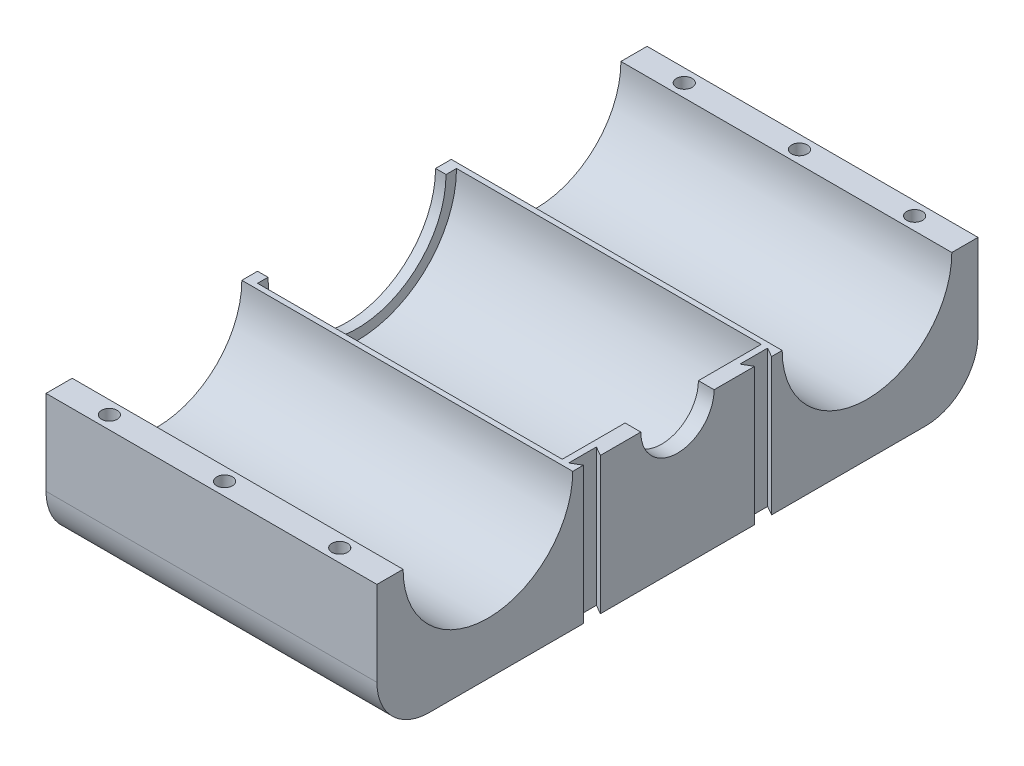
SolidWorks part; units mm, degrees
ref_plane "Front Plane" through (0, 0, 0) normal (0, 0, 1) x (1, 0, 0)
ref_plane "Top Plane" through (0, 0, 0) normal (0, 1, 0) x (1, 0, 0)
ref_plane "Right Plane" through (0, 0, 0) normal (1, 0, 0) x (0, 0, -1)
sketch "Sketch1" plane through (0, 0, 0) normal (1, 0, 0) x (0, 0, -1)
  line L0 (57.4, 42.0261) -> (57.4, 0) construction
  line L1 (0, 0) -> (114.8, 0)
  line L2 (0, 0) -> (0, 26.2)
  line L3 (114.8, 0) -> (114.8, 26.2)
  line L4 (0, 26.2) -> (5, 26.2) construction
  line L6 (37.4, 26.2) -> (77.4, 26.2) construction
  line L7 (37.4, 26.2) -> (77.4, 26.2)
  line L8 (0, 26.2) -> (5, 26.2)
  line L10 (37.4, 26.2) -> (77.4, 26.2)
  line L11 (109.8, 26.2) -> (114.8, 26.2)
  arc A0 (5, 26.2) -> (37.4, 26.2) centre (21.2, 26.2) ccw
  arc A1 (77.4, 26.2) -> (109.8, 26.2) centre (93.6, 26.2) ccw
  circle A2 centre (57.4, 13.245) radius 62.5 construction
  point P15 (93.6, 10)
  dimension "D4" = 16.2
  dimension "D3" = 16.2
  dimension "D6" = 125
  dimension "D1" = 5
  dimension "D5" = 10
  dimension "D2" = 40
extrude "Boss-Extrude1" add sketch "Sketch1" along normal blind 63.2 contours L8 L2 L1 L3 L7 region at (0, 10.7494, -57.4)
sketch "Sketch30" plane through (0, 26.2, 0) normal (0, 1, 0) x (1, 0, 0)
  line L0 (63.2, 57.4) -> (17.5829, 57.4) construction
  line L1 (63.2, 37.4) -> (63.2, 77.4) construction
  line L2 (63.2, 75.375) -> (61.4246, 76.4)
  line L3 (61.4246, 76.4) -> (61.4246, 71.1)
  line L4 (61.4246, 71.1) -> (63.2, 72.125)
  line L5 (63.2, 42.675) -> (61.4246, 43.7)
  line L6 (61.4246, 43.7) -> (61.4246, 38.4)
  line L7 (61.4246, 38.4) -> (63.2, 39.425)
  line L8 (63.2, 75.375) -> (63.2, 72.125)
  line L9 (63.2, 42.675) -> (63.2, 39.425)
  line L10 (63.2, 77.4) -> (0, 77.4) construction
  line L12 (63.2, 37.4) -> (0, 37.4) construction
  dimension "D1" = 5.3
  dimension "D2" = 60
  dimension "D3" = 60
  dimension "D4" = 3.25
  dimension "D5" = 60
  dimension "D6" = 1
  dimension "D7" = 1
extrude "Cut-Extrude14" cut sketch "Sketch30" against normal up to next
sketch "Sketch31" plane through (0, 0, 0) normal (-1, 0, 0) x (0, 0, 1)
  line L0 (-37.4, 26.2) -> (-77.4, 26.2) construction
  circle A0 centre (-57.4, 26.2) radius 19
  dimension "D1" = 38
extrude "Cut-Extrude15" cut sketch "Sketch31" against normal offset from surface (60.2 mm away) 3 contours A0 up to face at (63.2, 13.1, -57.4)
sketch "Sketch32" plane through (63.2, 0, 0) normal (1, 0, 0) x (0, 0, -1)
  line L0 (42.675, 26.2) -> (72.125, 26.2) construction
  circle A0 centre (57.4, 26.2) radius 7
  dimension "D1" = 14
extrude "Cut-Extrude16" cut sketch "Sketch32" against normal up to next
sketch "Sketch33" plane through (0, 0, 0) normal (-1, 0, 0) x (0, 0, 1)
  line L0 (-74.4, 26.2) -> (-76.4, 26.2)
  line L1 (-40.4, 26.2) -> (-38.4, 26.2)
  arc A1 (-76.4, 26.2) -> (-38.4, 26.2) centre (-57.4, 26.2) ccw construction
  arc A2 (-74.4, 26.2) -> (-40.4, 26.2) centre (-57.4, 26.2) ccw
  arc A3 (-74.4, 26.2) -> (-40.4, 26.2) centre (-57.4, 26.2) ccw
  arc A4 (-76.4, 26.2) -> (-38.4, 26.2) centre (-57.4, 26.2) ccw
  dimension "D1" = 2
extrude "Boss-Extrude6" add sketch "Sketch33" against normal blind 2
fillet "Fillet1" radius 10 2 edges at (31.6, 0, -114.8) (31.6, 0, 0)
sketch "Sketch34" plane through (0, 26.2, 0) normal (0, 1, 0) x (1, 0, 0)
  line L0 (0, 112.3) -> (63.2, 112.3) construction
  line L1 (0, 109.8) -> (0, 114.8) construction
  line L2 (63.2, 109.8) -> (63.2, 114.8) construction
  line L3 (63.2, 57.4) -> (76.2618, 57.4) construction
  line L4 (63.2, 50.4) -> (63.2, 64.4) construction
  circle A0 centre (9.6, 112.3) radius 1.5
  circle A1 centre (31.6, 112.3) radius 1.5
  circle A2 centre (53.6, 112.3) radius 1.5
  circle A3 centre (53.6, 2.5) radius 1.5
  circle A4 centre (31.6, 2.5) radius 1.5
  circle A5 centre (9.6, 2.5) radius 1.5
  dimension "D1" = 3
  dimension "D2" = 22
  dimension "D3" = 22
extrude "Cut-Extrude17" cut sketch "Sketch34" against normal blind 15
sketch "Sketch35" plane through (0, 0, 0) normal (0, -1, 0) x (1, 0, 0)
  line L0 (31.6, -10) -> (31.6, -104.8) construction
  line L1 (16.0672, -30.106) -> (47.1328, -30.106) construction
  line L2 (16.0672, -30.106) -> (16.0672, -86.0987) construction
  line L3 (16.0672, -86.0987) -> (47.1328, -86.0987) construction
  line L4 (47.1328, -30.106) -> (47.1328, -86.0987) construction
  line L5 (63.2, -10) -> (0, -10) construction
  line L6 (0, -104.8) -> (63.2, -104.8) construction
  line L7 (63.2, -10) -> (63.2, -39.425) construction
  line L8 (63.2, -114.8) -> (0, -114.8) construction
  line L9 (0, 0) -> (63.2, 0) construction
  circle A0 centre (16.0672, -30.106) radius 2.3
  circle A1 centre (47.1328, -30.106) radius 2.3
  circle A2 centre (16.0672, -86.0987) radius 2.3
  circle A3 centre (47.1328, -86.0987) radius 2.3
  point P8 (31.6, -30.106)
  dimension "D1" = 4.6
  dimension "D2" = 4.6
  dimension "D3" = 4.6
  dimension "D4" = 4.6
  dimension "D5" = 55.9927
  dimension "D6" = 31.0656
  dimension "D7" = 16.0672
  dimension "D8" = 28.7013
extrude "Cut-Extrude18" cut sketch "Sketch35" against normal blind 6
equation "\"MotorDIA\"= 37' Motor Diameter"
equation "\"SyringeDIA\"= 31.4'60ml Syringe Diameter"
equation "\"MotorShaftDIA\"= 6'Motor Shaft Dia"
equation "\"MotorKeyway\"= 1'Motor Shaft Keyway Depth"
equation "\"MotorLength\"= 56.7'Motor Length Excluding Shaft"
equation "\"SyringeLength\"= 117.3'60ml Syringe Length Excluding Nozzle"
equation "\"3Dtol\"= .5'Sizing Tolerance for 3D printed parts"
equation "\"ChamberDIA\"= 100 - 4'Buoyancy Chamber inner Diameter"
equation "\"ChamberThk\"= 2mm'Buoyancy Chamber Wall Thickness"
equation "\"D1@Boss-Extrude1\"=\"MotorLength\"+\"3Dtol\"+4"
equation "\"BearingOD\"= 10"
equation "\"BearingID\"= 4"
equation "\"Bearingwidth\"= 4"
equation "\"ShaftDIA\"= 4"
equation "\"D3@Sketch1\"=\"D4@Sketch1\""
